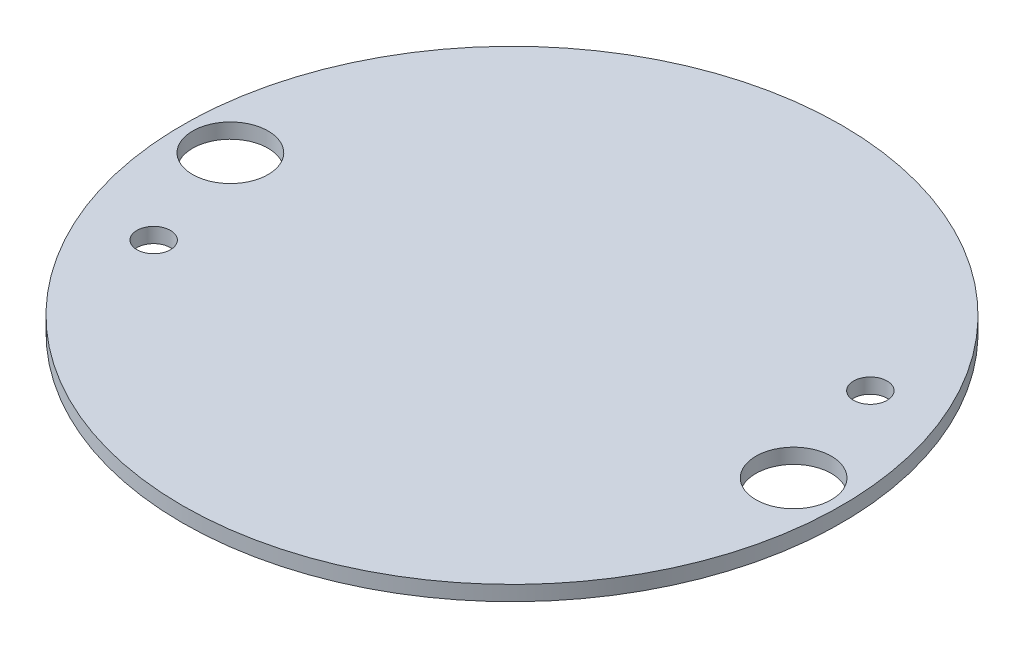
SolidWorks part; units mm, degrees
ref_plane "Front Plane" through (0, 0, 0) normal (0, 0, 1) x (1, 0, 0)
ref_plane "Top Plane" through (0, 0, 0) normal (0, 1, 0) x (1, 0, 0)
ref_plane "Right Plane" through (0, 0, 0) normal (1, 0, 0) x (0, 0, -1)
sketch "Sketch1" plane through (0, 0, 0) normal (0, 1, 0) x (1, 0, 0)
  circle A0 centre (0, 0) radius 69.85
extrude "Boss-Extrude1" add sketch "Sketch1" along normal blind 3.175
sketch "Sketch2" plane through (0, 3.175, 0) normal (0, 1, 0) x (1, 0, 0)
  line L0 (59.69, 0) -> (-59.69, 0) construction
  line L1 (51.7955, 24.1526) -> (-51.7955, -24.1526)
  circle A0 centre (-59.69, 0) radius 8.001
  circle A1 centre (59.69, 0) radius 8.001
  circle A2 centre (-51.7955, -24.1526) radius 3.556
  circle A3 centre (51.7955, 24.1526) radius 3.556
  point P4 (0, 0)
  point P10 (0, 0)
extrude "Cut-Extrude1" cut sketch "Sketch2" against normal blind 3.175 contours A2 | A0 | A1 | A3 region at (-48.422, 3.175, 23.4047) region at (51.0476, 3.175, -27.5261) region at (-59.69, 3.175, 0) region at (59.69, 3.175, 0)
